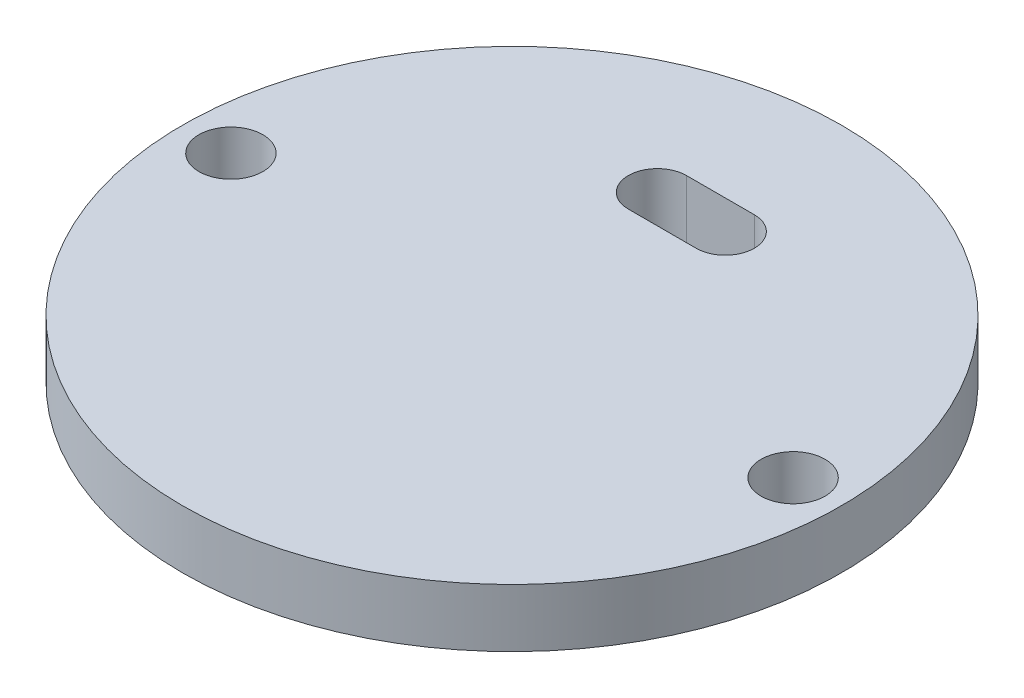
SolidWorks part; units mm, degrees
material "Pine"
ref_plane "Front Plane" through (0, 0, 0) normal (0, 0, 1) x (1, 0, 0)
ref_plane "Top Plane" through (0, 0, 0) normal (0, 1, 0) x (1, 0, 0)
ref_plane "Right Plane" through (0, 0, 0) normal (1, 0, 0) x (0, 0, -1)
sketch "Sketch1" plane through (0, 0, 0) normal (0, 1, 0) x (1, 0, 0)
  line L0 (-1.75, 9.083) -> (-1.75, 10.75) construction
  line L1 (-1.75, 7.75) -> (1.75, 7.75)
  line L2 (-1.75, 7.75) -> (-1.75, 9.083) construction
  line L3 (-1.75, 10.75) -> (1.75, 10.75)
  line L4 (1.75, 7.75) -> (1.75, 9.083) construction
  line L5 (-1.75, 7.75) -> (-0.2676, 9.0206) construction
  line L6 (-1.75, 10.75) -> (-0.2676, 9.4794) construction
  line L7 (-0.2676, 9.4794) -> (0, 9.25) construction
  line L8 (0.2676, 9.0206) -> (1.75, 7.75) construction
  line L9 (0, 9.25) -> (0.2676, 9.4794) construction
  line L10 (0.2676, 9.4794) -> (1.75, 10.75) construction
  line L11 (1.75, 9.083) -> (1.75, 10.75) construction
  line L12 (0, 9.25) -> (0.2676, 9.0206) construction
  line L13 (-0.2676, 9.0206) -> (0, 9.25) construction
  line L14 (-14.5, 0) -> (14.5, 0) construction
  circle A0 centre (0, 0) radius 17
  circle A1 centre (0, 0) radius 9.25 construction
  arc A2 (1.75, 7.75) -> (1.75, 10.75) centre (1.75, 9.25) ccw
  arc A3 (-1.75, 10.75) -> (-1.75, 7.75) centre (-1.75, 9.25) ccw
  arc A4 (-0.25, 9.2466) -> (-0.2676, 9.4794) centre (-1.75, 9.25) ccw construction
  arc A5 (-0.2676, 9.4794) -> (-1.75, 10.75) centre (-1.75, 9.25) ccw construction
  arc A6 (0.2676, 9.4794) -> (0.25, 9.2466) centre (1.75, 9.25) ccw construction
  arc A7 (1.75, 10.75) -> (0.2676, 9.4794) centre (1.75, 9.25) ccw construction
  arc A8 (0.25, 9.2466) -> (0.2676, 9.0206) centre (1.75, 9.25) ccw construction
  arc A9 (0.2676, 9.0206) -> (1.75, 7.75) centre (1.75, 9.25) ccw construction
  arc A10 (-0.2676, 9.0206) -> (-0.25, 9.2466) centre (-1.75, 9.25) ccw construction
  arc A11 (-1.75, 7.75) -> (-0.2676, 9.0206) centre (-1.75, 9.25) ccw construction
  circle A12 centre (-14.5, 0) radius 1.65
  circle A13 centre (14.5, 0) radius 1.65
  point P4 (0, 9.25)
  point P23 (0, 0)
  dimension "D1" = 34
  dimension "D2" = 18.5
  dimension "D5" = 3.3
  dimension "D3" = 3.5
  dimension "D4" = 3
  dimension "D6" = 29
extrude "Boss-Extrude1" add sketch "Sketch1" along normal blind 3
